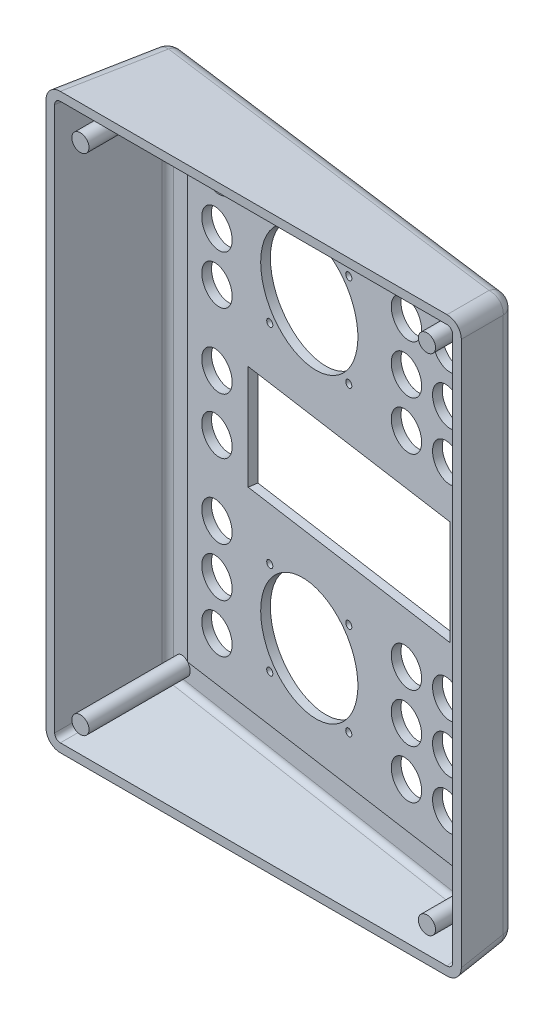
SolidWorks part; units mm, degrees
ref_plane "Спереди" through (0, 0, 0) normal (0, 0, 1) x (1, 0, 0)
ref_plane "Сверху" through (0, 0, 0) normal (0, 1, 0) x (1, 0, 0)
ref_plane "Справа" through (0, 0, 0) normal (1, 0, 0) x (0, 0, -1)
sketch "Sketch1" plane through (0, 0, 0) normal (0, 0, 1) x (1, 0, 0)
  line L0 (0, 100) -> (0, -100) construction
  line L1 (72.5, -100) -> (-72.5, -100)
  line L2 (72.5, -100) -> (72.5, 100)
  line L3 (72.5, 100) -> (-72.5, 100)
  line L4 (-72.5, -100) -> (-72.5, 100)
  line L5 (-72.5, 0) -> (72.5, 0) construction
  dimension "D1" = 145
  dimension "D2" = 200
extrude "Boss-Extrude1" add sketch "Sketch1" against normal blind 40 draft 5
sketch "Sketch2" plane through (0, 0, 0) normal (0, 1, 0) x (1, 0, 0)
  line L0 (-69.0005, 40) -> (70.7502, 20)
  line L1 (69.0005, 40) -> (72.5, 0) construction
  line L2 (69.0005, 40) -> (-69.0005, 40) construction
  line L3 (69.0005, 40) -> (70.7502, 20)
  line L4 (69.0005, 40) -> (-69.0005, 40)
extrude "Cut-Extrude1" cut sketch "Sketch2" against normal through all and the other way through all
fillet "Fillet1" radius 5 4 edges at (71.6251, -99.1251, -10) (-70.7502, -98.2502, -20) (71.6251, 99.1251, -10) (-70.7502, 98.2502, -20)
fillet "Fillet2" radius 5 8 edges at (-67.5619, 95.0619, -39.7941) (-69.0005, 0, -40) (-67.5619, -95.0619, -39.7941) (0.8125, -97.3746, -30.0089) (69.2752, -96.7752, -20.2111) (70.7502, 0, -20) (69.2752, 96.7752, -20.2111) (0.8125, 97.3746, -30.0089)
sketch "Sketch3" plane through (4.2248, 0, -29.5206) normal (0.1417, 0, -0.9899) x (-0.9899, 0, -0.1417)
  line L0 (-63.2364, 0) -> (68.6891, 0) construction
  line L1 (-54.2737, 82.5) -> (59.7263, 82.5)
  line L2 (-54.2737, 82.5) -> (-54.2737, -82.5)
  line L3 (-54.2737, -82.5) -> (59.7263, -82.5)
  line L4 (59.7263, 82.5) -> (59.7263, -82.5)
  line L5 (-63.2364, 93.615) -> (-63.2364, -93.615) construction
  line L6 (68.6891, -91.9799) -> (68.6891, 91.9799) construction
  line L7 (2.7263, 92.7974) -> (2.7263, -92.7974) construction
  line L8 (68.6891, 91.9799) -> (-63.2364, 93.615) construction
  line L9 (-63.2364, -93.615) -> (68.6891, -91.9799) construction
  dimension "D1" = 165
  dimension "D2" = 114
extrude "Cut-Extrude2" cut sketch "Sketch3" against normal blind 0.5 draft 5
shell "Shell1" thickness 3 removed face at (0, 0, 0)
sketch "Sketch4" plane through (0, 0, 0) normal (0, 0, 1) x (1, 0, 0)
  circle A0 centre (-60.5, 88) radius 3
  circle A1 centre (60.5, 88) radius 3
  circle A2 centre (-60.5, -88) radius 3
  circle A3 centre (60.5, -88) radius 3
  dimension "D1" = 6
extrude "Boss-Extrude2" add sketch "Sketch4" against normal up to surface (35.3236 mm away) up to face at (1.1009, 0, -26.9371)
sketch "Sketch5" plane through (4.1539, 0, -29.0256) normal (0.1417, 0, -0.9899) x (-0.9899, 0, -0.1417)
  line L1 (59.6826, 0) -> (-54.2299, 0) construction
  line L3 (-54.2299, 82.4563) -> (-54.2299, -82.4563) construction
  line L7 (2.7263, -82.4563) -> (2.7263, 82.4563) construction
  line L8 (-54.2299, 82.4563) -> (-54.2299, -82.4563) construction
  line L9 (-54.2299, -82.4563) -> (59.6826, -82.4563) construction
  line L10 (59.6826, -82.4563) -> (59.6826, 82.4563) construction
  line L11 (59.6826, 82.4563) -> (-54.2299, 82.4563) construction
  line L12 (-45.6237, -18.25) -> (37.3763, -18.25)
  line L13 (-45.6237, -18.25) -> (-45.6237, 18.25)
  line L14 (-45.6237, 18.25) -> (37.3763, 18.25)
  line L15 (37.3763, -18.25) -> (37.3763, 18.25)
  line L16 (50.2263, -69.7063) -> (50.2263, 82.4563) construction
  line L17 (-27.7737, -69.7063) -> (-27.7737, 82.4563) construction
  line L18 (-44.7737, -69.7063) -> (-44.7737, 82.4563) construction
  line L19 (50.2263, -52.7063) -> (-44.7737, -52.7063) construction
  line L20 (50.2263, -69.7063) -> (-44.7737, -69.7063) construction
  line L21 (12.2263, -82.4563) -> (12.2263, 82.4563) construction
  line L22 (28.4898, -36.4428) -> (-4.0371, -68.9697) construction
  line L23 (28.4898, -68.9697) -> (-4.0371, -36.4428) construction
  line L24 (-44.7737, -35.7063) -> (50.2263, -35.7063) construction
  line L25 (-4.1237, -18.25) -> (-4.1237, 18.25) construction
  circle A0 centre (50.2263, -69.7063) radius 6.25
  circle A1 centre (50.2263, -52.7063) radius 6.25
  circle A2 centre (50.2263, -35.7063) radius 6.25
  circle A3 centre (50.2263, -9.75) radius 6.25
  circle A4 centre (-27.7737, -69.7063) radius 6.25
  circle A5 centre (-44.7737, -69.7063) radius 6.25
  circle A6 centre (-27.7737, -52.7063) radius 6.25
  circle A7 centre (-27.7737, -35.7063) radius 6.25
  circle A8 centre (-44.7737, -35.7063) radius 6.25
  circle A9 centre (-44.7737, -52.7063) radius 6.25
  circle A10 centre (28.4898, -68.9697) radius 1.25
  circle A11 centre (-4.0371, -68.9697) radius 1.25
  circle A12 centre (-4.0371, -36.4428) radius 1.25
  circle A13 centre (28.4898, -36.4428) radius 1.25
  circle A14 centre (12.2263, -52.7063) radius 20
  circle A15 centre (12.2263, -52.7063) radius 23 construction
  circle A16 centre (-44.7737, 35.7063) radius 6.25
  circle A17 centre (-44.7737, 52.7063) radius 6.25
  circle A18 centre (-44.7737, 69.7063) radius 6.25
  circle A19 centre (-27.7737, 69.7063) radius 6.25
  circle A20 centre (-27.7737, 35.7063) radius 6.25
  circle A21 centre (-27.7737, 52.7063) radius 6.25
  circle A22 centre (-4.0371, 36.4428) radius 1.25
  circle A23 centre (-4.0371, 68.9697) radius 1.25
  circle A24 centre (28.4898, 68.9697) radius 1.25
  circle A25 centre (28.4898, 36.4428) radius 1.25
  circle A26 centre (12.2263, 52.7063) radius 20
  circle A27 centre (50.2263, 9.75) radius 6.25
  circle A28 centre (50.2263, 35.7063) radius 6.25
  circle A29 centre (50.2263, 52.7063) radius 6.25
  circle A30 centre (50.2263, 69.7063) radius 6.25
  point P7 (-54.2299, 0)
  point P77 (12.2263, -52.7063)
  point P78 (12.2263, -52.7063)
  point P84 (12.2263, -52.7063)
  dimension "D1" = 12.5
  dimension "D4" = 40
  dimension "D11" = 2.5
  dimension "D7" = 3
  dimension "D2" = 113.9125
  dimension "D3" = 164.9125
  dimension "D5" = 36.5
  dimension "D6" = 83
  dimension "D8" = 52.7063
  dimension "D9" = 45
  dimension "D10" = 9.5
  dimension "D12" = 38
  dimension "D13" = 40
  dimension "D14" = 17
  dimension "D15" = 17
  dimension "D16" = 17
  dimension "D17" = 9.75
  dimension "D18" = 6.85
extrude "Cut-Extrude3" cut sketch "Sketch5" against normal through all both and the other way through all
